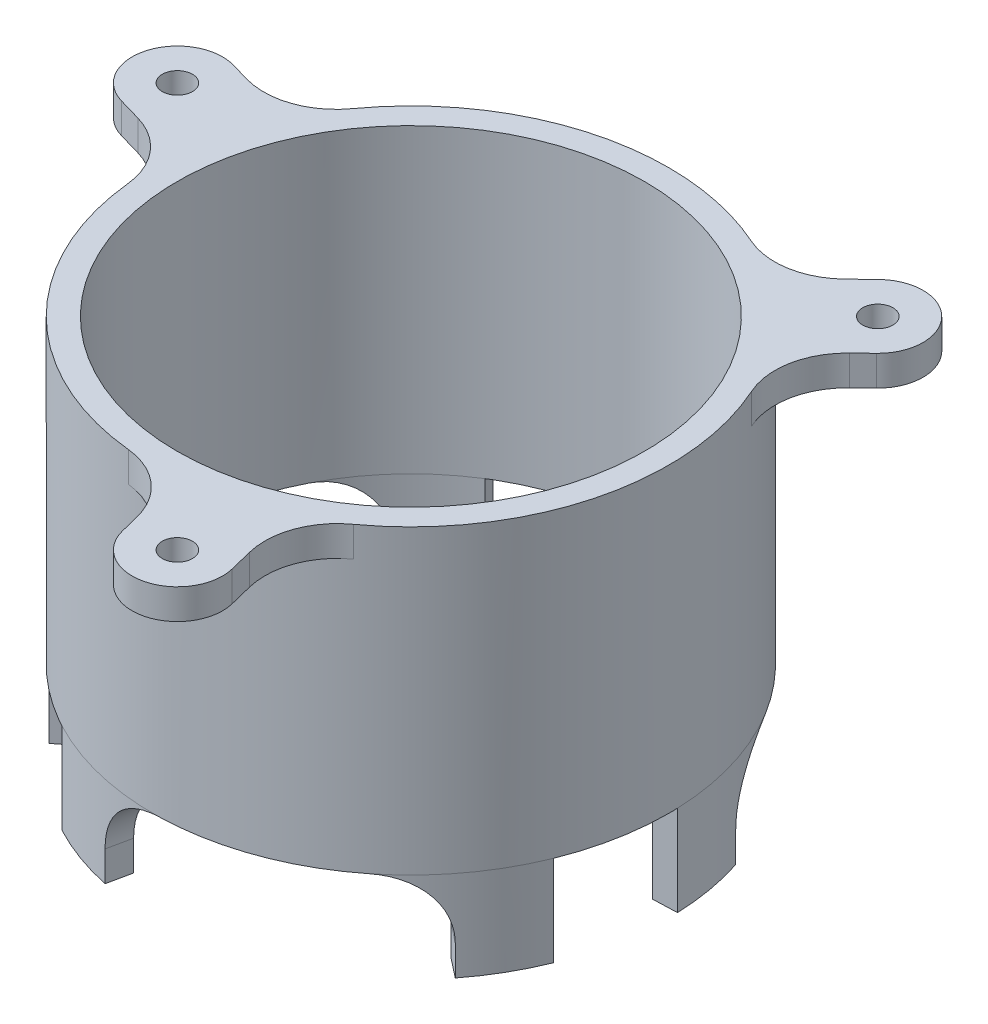
SolidWorks part; units mm, degrees
ref_plane "Front Plane" through (0, 0, 0) normal (0, 0, 1) x (1, 0, 0)
ref_plane "Top Plane" through (0, 0, 0) normal (0, 1, 0) x (1, 0, 0)
ref_plane "Right Plane" through (0, 0, 0) normal (1, 0, 0) x (0, 0, -1)
sketch "Sketch1" plane through (0, 0, 0) normal (0, 1, 0) x (1, 0, 0)
  circle A0 centre (0, 0) radius 38.75
  circle A1 centre (0, 0) radius 42.75
  dimension "D1" = 77.5
  dimension "D2" = 4
extrude "Boss-Extrude1" add sketch "Sketch1" along normal blind 50
sketch "Sketch2" plane through (0, 0, 0) normal (0, -1, 0) x (1, 0, 0)
  line L0 (0, 0) -> (40.1719, 14.6214) construction
  line L1 (0, 0) -> (42.75, 0) construction
  line L2 (40.1719, 14.6214) -> (36.4131, 13.2533) construction
  line L3 (38.75, 0) -> (42.75, 0) construction
  line L4 (-7.4235, -42.1005) -> (-6.7289, -38.1613) construction
  line L5 (-19.375, -33.5585) -> (-21.375, -37.0226) construction
  line L6 (-32.7484, 27.4792) -> (-29.6842, 24.908) construction
  line L7 (-19.375, 33.5585) -> (-21.375, 37.0226) construction
  line L8 (0, 0) -> (33.6875, 26.3195) construction
  line L9 (0, 0) -> (40.6577, -13.2105) construction
  line L10 (38.75, 0) -> (42.75, 0)
  line L11 (40.6577, -13.2105) -> (36.8534, -11.9744)
  line L12 (30.5354, 23.8569) -> (33.6875, 26.3195)
  line L13 (40.1719, 14.6214) -> (36.4131, 13.2533)
  line L14 (-7.4235, -42.1005) -> (-6.7289, -38.1613)
  line L15 (5.393, -38.3729) -> (5.9496, -42.334)
  line L16 (-31.7694, -28.6053) -> (-28.7969, -25.9288)
  line L17 (-19.375, -33.5585) -> (-21.375, -37.0226)
  line L18 (-32.7484, 27.4792) -> (-29.6842, 24.908)
  line L19 (-35.9284, 14.516) -> (-39.6371, 16.0144)
  line L20 (-8.8882, 41.8158) -> (-8.0566, 37.9032)
  line L21 (-19.375, 33.5585) -> (-21.375, 37.0226)
  circle A0 centre (0, 0) radius 42.75 construction
  circle A1 centre (0, 0) radius 38.75 construction
  arc A2 (38.75, 0) -> (36.4131, 13.2533) centre (0, 0) ccw construction
  arc A3 (42.75, 0) -> (40.1719, 14.6214) centre (0, 0) ccw construction
  arc A4 (-21.375, -37.0226) -> (-7.4235, -42.1005) centre (0, 0) ccw construction
  arc A5 (-19.375, -33.5585) -> (-6.7289, -38.1613) centre (0, 0) ccw construction
  arc A6 (-21.375, 37.0226) -> (-32.7484, 27.4792) centre (0, 0) ccw construction
  arc A7 (-19.375, 33.5585) -> (-29.6842, 24.908) centre (0, 0) ccw construction
  arc A8 (36.4131, 13.2533) -> (30.5354, 23.8569) centre (0, 0) ccw
  arc A9 (40.1719, 14.6214) -> (33.6875, 26.3195) centre (0, 0) ccw
  arc A10 (38.75, 0) -> (36.8534, -11.9744) centre (0, 0) cw
  arc A11 (42.75, 0) -> (40.6577, -13.2105) centre (0, 0) cw
  arc A12 (-6.7289, -38.1613) -> (5.393, -38.3729) centre (0, 0) ccw
  arc A13 (-7.4235, -42.1005) -> (5.9496, -42.334) centre (0, 0) ccw
  arc A14 (-19.375, -33.5585) -> (-28.7969, -25.9288) centre (0, 0) cw
  arc A15 (-21.375, -37.0226) -> (-31.7694, -28.6053) centre (0, 0) cw
  arc A16 (-29.6842, 24.908) -> (-35.9284, 14.516) centre (0, 0) ccw
  arc A17 (-32.7484, 27.4792) -> (-39.6371, 16.0144) centre (0, 0) ccw
  arc A18 (-19.375, 33.5585) -> (-8.0566, 37.9032) centre (0, 0) cw
  arc A19 (-21.375, 37.0226) -> (-8.8882, 41.8158) centre (0, 0) cw
  point P24 (0, 0)
  point P57 (0, 0)
  dimension "D1" = 20
  dimension "D3" = 18
  dimension "D4" = 18
  dimension "D2" = 3
  dimension "D5" = 3
extrude "Boss-Extrude3" add sketch "Sketch2" along normal blind 15
fillet "Fillet11" radius 10 6 edges at (-30.2832, 0, -27.2671) (5.6713, 0, -40.3534) (32.1114, 0, 25.0882) (38.7556, 0, -12.5924) (-8.4724, 0, 39.8595) (-37.7827, 0, 15.2652)
sketch "Sketch3" plane through (0, 50, 0) normal (0, 1, 0) x (1, 0, 0)
  line L0 (0, 0) -> (30.2288, 30.2288) construction
  line L1 (0, 0) -> (2.9302, 0) construction
  line L2 (30.2288, 30.2288) -> (38.7141, 38.7141) construction
  line L3 (33.5116, 44.1164) -> (43.9166, 33.3118) construction
  line L4 (33.5116, 44.1164) -> (21.3089, 32.365)
  line L5 (43.9166, 33.3118) -> (32.0071, 21.8428)
  line L6 (21.4501, -51.0801) -> (17.3744, -34.6366)
  line L7 (6.8906, -54.6888) -> (2.9129, -38.6404)
  line L8 (-54.9617, 6.9638) -> (-38.6834, 2.2716)
  line L9 (-50.8072, 21.3769) -> (-34.92, 16.7975)
  circle A0 centre (0, 0) radius 42.75 construction
  circle A1 centre (38.7141, 38.7141) radius 2.5
  arc A2 (43.9166, 33.3118) -> (33.5116, 44.1164) centre (38.7141, 38.7141) ccw
  circle A3 centre (0, 0) radius 38.75 construction
  arc A4 (32.0071, 21.8428) -> (21.3089, 32.365) centre (0, 0) ccw
  arc A5 (6.8906, -54.6888) -> (21.4501, -51.0801) centre (14.1703, -52.8844) ccw
  arc A6 (2.9129, -38.6404) -> (17.3744, -34.6366) centre (0, 0) ccw
  circle A7 centre (14.1703, -52.8844) radius 2.5
  arc A8 (-50.8072, 21.3769) -> (-54.9617, 6.9638) centre (-52.8844, 14.1703) ccw
  arc A9 (-34.92, 16.7975) -> (-38.6834, 2.2716) centre (0, 0) ccw
  circle A10 centre (-52.8844, 14.1703) radius 2.5
  point P11 (38.7141, 38.7141)
  point P31 (0, 0)
  dimension "D2" = 5
  dimension "D3" = 5
  dimension "D1" = 45
  dimension "D4" = 12
  dimension "D5" = 3
extrude "Boss-Extrude4" add sketch "Sketch3" against normal blind 5
fillet "Fillet12" radius 12 6 edges at (3.8876, 47.5, 42.5729) (18.3586, 47.5, 38.6073) (34.9254, 47.5, -24.6532) (24.2556, 47.5, -35.2027) (-38.813, 47.5, -17.9197) (-42.6142, 47.5, -3.4046)
sketch "Sketch4" plane through (0, 0, 0) normal (0, 1, 0) x (1, 0, 0)
  line L0 (0, 0) -> (-6.7289, 38.1613) construction
  line L1 (0, 0) -> (-19.375, 33.5585) construction
  line L2 (0, 0) -> (-5.9497, 42.334) construction
  line L3 (0, 0) -> (-22.654, 36.2541) construction
  line L4 (-20.5344, 32.8619) -> (-22.654, 36.2541)
  line L5 (-5.9497, 42.334) -> (-5.393, 38.3729)
  line L6 (38.7264, 1.3524) -> (42.724, 1.492)
  line L7 (39.6371, -16.0144) -> (35.9284, -14.516)
  line L8 (-18.192, -34.2142) -> (-20.0699, -37.746)
  line L9 (-33.6875, -26.3195) -> (-30.5354, -23.8569)
  arc A3 (-5.393, 38.3729) -> (-20.5344, 32.8619) centre (0, 0) ccw
  arc A4 (-6.7289, 38.1613) -> (-19.375, 33.5585) centre (0, 0) ccw construction
  arc A5 (-5.9497, 42.334) -> (-22.654, 36.2541) centre (-9.0911, 24.9776) ccw
  arc A7 (39.6371, -16.0144) -> (42.724, 1.492) centre (26.1768, -4.6157) ccw
  arc A8 (35.9284, -14.516) -> (38.7264, 1.3524) centre (0, 0) ccw
  arc A9 (-33.6875, -26.3195) -> (-20.0699, -37.746) centre (-17.0857, -20.3619) ccw
  arc A10 (-30.5354, -23.8569) -> (-18.192, -34.2142) centre (0, 0) ccw
  point P8 (0, 0)
  point P24 (0, 0)
  point P25 (0, 0)
  point P37 (0, 0)
  dimension "D1" = 2
  dimension "D2" = 2
  dimension "D3" = 3
extrude "Cut-Extrude1" cut sketch "Sketch4" against normal through all
